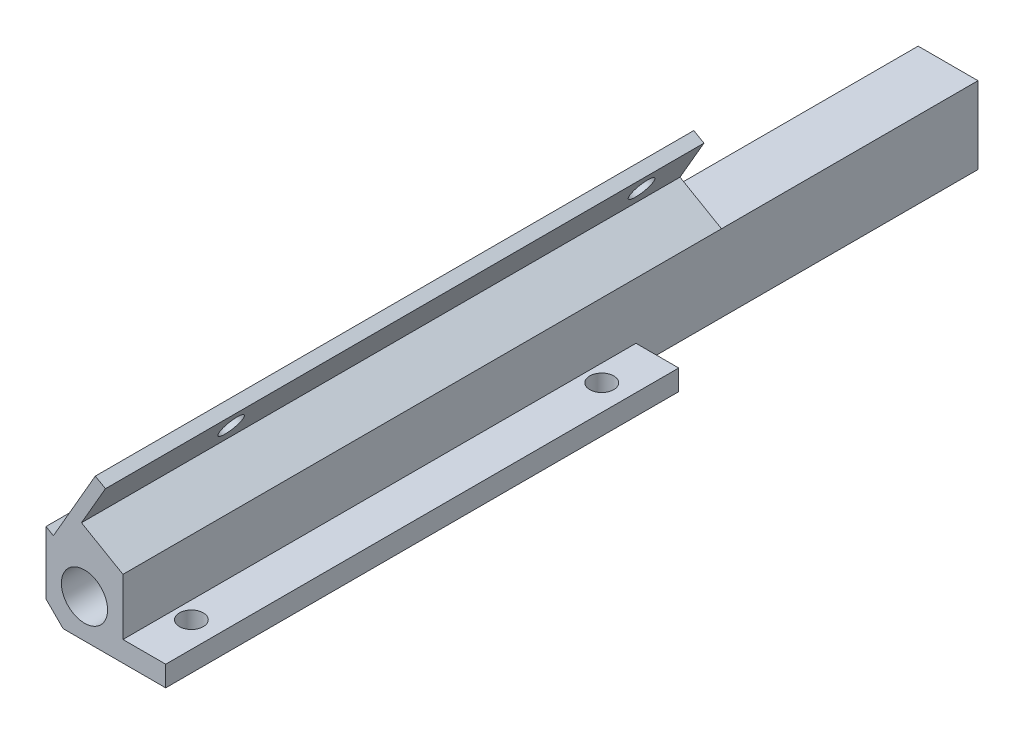
SolidWorks part; units mm, degrees
ref_plane "Front Plane" through (0, 0, 0) normal (0, 0, 1) x (1, 0, 0)
ref_plane "Top Plane" through (0, 0, 0) normal (0, 1, 0) x (1, 0, 0)
ref_plane "Right Plane" through (0, 0, 0) normal (1, 0, 0) x (0, 0, -1)
sketch "Sketch1" plane through (0, 0, 0) normal (0, 1, 0) x (1, 0, 0)
  line L1 (0, 0) -> (77.47, 0)
  line L2 (0, 0) -> (0, 127)
  line L3 (0, 127) -> (77.47, 127)
  line L4 (77.47, 0) -> (77.47, 127)
  dimension "D1" = 77.47
  dimension "D2" = 127
extrude "Boss-Extrude1" add sketch "Sketch1" along normal blind 11.43
sketch "Sketch2" plane through (0, 0, 0) normal (0, 0, 1) x (1, 0, 0)
  line L0 (5.715, 5.715) -> (71.755, 5.715) construction
  line L1 (38.735, 11.43) -> (38.735, 0) construction
  line L2 (0, 11.43) -> (77.47, 11.43) construction
  line L3 (0, 0) -> (77.47, 0) construction
  circle A0 centre (5.715, 5.715) radius 3.429
  circle A1 centre (71.755, 5.715) radius 3.429
  point P10 (38.735, 5.715)
  dimension "D1" = 6.858
  dimension "D2" = 66.04
extrude "Cut-Extrude1" cut sketch "Sketch2" against normal through all
sketch "Sketch3" plane through (0, 11.43, 0) normal (0, 1, 0) x (1, 0, 0)
  line L0 (11.43, 127) -> (11.43, 88.9)
  line L1 (77.47, 127) -> (0, 127) construction
  line L2 (11.43, 127) -> (66.04, 127)
  line L3 (66.04, 127) -> (66.04, 88.9)
  line L4 (53.34, 76.2) -> (24.13, 76.2)
  line L5 (0, 127) -> (0, 0) construction
  arc A0 (66.04, 88.9) -> (53.34, 76.2) centre (53.34, 88.9) cw
  arc A1 (24.13, 76.2) -> (11.43, 88.9) centre (24.13, 88.9) cw
  point P10 (38.735, 127)
  dimension "D1" = 12.7
  dimension "D2" = 11.43
  dimension "D3" = 50.8
extrude "Cut-Extrude2" cut sketch "Sketch3" against normal through all
sketch "Sketch4" plane through (0, 0, -127) normal (0, 0, -1) x (-1, 0, 0)
  line L0 (-11.43, 0) -> (-11.43, 11.43) construction
  line L1 (-66.04, 11.43) -> (-11.43, 11.43)
  line L2 (-66.04, 11.43) -> (-66.04, 5.08)
  line L3 (-66.04, 5.08) -> (-11.43, 5.08)
  line L4 (-11.43, 11.43) -> (-11.43, 5.08)
  line L5 (-11.43, 0) -> (0, 0) construction
  dimension "D1" = 5.08
extrude "Cut-Extrude3" cut sketch "Sketch4" against normal through all
chamfer "Chamfer1" distance 2.54 angle 45 4 edges at (0, 0, -63.5) (0, 11.43, -63.5) (77.47, 0, -63.5) (77.47, 11.43, -63.5)
sketch "Sketch5" plane through (0, 11.43, 0) normal (0, 1, 0) x (1, 0, 0)
  line L0 (11.43, 88.9) -> (11.43, 76.2)
  line L1 (11.43, 0) -> (11.43, 88.9) construction
  line L2 (11.43, 76.2) -> (77.47, 76.2)
  line L3 (77.47, 127) -> (77.47, 0) construction
  line L4 (77.47, 76.2) -> (77.47, 127)
  line L8 (24.13, 76.2) -> (53.34, 76.2) construction
  line L9 (77.47, 127) -> (11.43, 127)
  line L10 (11.43, 127) -> (11.43, 88.9)
extrude "Cut-Extrude4" cut sketch "Sketch5" against normal through all
sketch "Sketch6" plane through (0, 11.43, 0) normal (0, 1, 0) x (1, 0, 0)
  line L0 (24.13, 76.2) -> (24.13, 0)
  line L1 (11.43, 76.2) -> (66.04, 76.2) construction
  line L2 (66.04, 0) -> (11.43, 0) construction
  line L3 (24.13, 0) -> (77.47, 0)
  line L4 (77.47, 0) -> (77.47, 76.2)
  line L5 (77.47, 76.2) -> (24.13, 76.2)
  line L6 (11.43, 0) -> (11.43, 76.2) construction
  dimension "D1" = 12.7
extrude "Cut-Extrude5" cut sketch "Sketch6" against normal through all
sketch "Sketch7" plane through (0, 5.08, 0) normal (0, 1, 0) x (1, 0, 0)
  line L0 (11.43, 76.2) -> (24.13, 76.2) construction
  line L1 (11.43, 0) -> (11.43, 76.2) construction
  circle A0 centre (13.97, 68.58) radius 1.778
  circle A1 centre (13.97, 7.62) radius 1.778
  dimension "D1" = 3.556
  dimension "D2" = 7.62
  dimension "D3" = 68.58
  dimension "D4" = 2.54
extrude "Hole Cuts 1" cut sketch "Sketch7" against normal through all
sketch "Sketch17" plane through (0, 0, 0) normal (0, 0, 1) x (1, 0, 0)
  line L0 (0, 8.89) -> (0, 11.8699)
  line L1 (0, 11.8699) -> (5.588, 21.5486)
  line L2 (5.588, 21.5486) -> (8.8517, 19.6643)
  line L3 (8.8517, 19.6643) -> (5.9307, 14.605)
  line L4 (5.9307, 14.605) -> (11.43, 11.43)
  line L5 (0, 8.89) -> (0, 2.54) construction
  line L6 (11.43, 11.43) -> (2.54, 11.43)
  line L7 (2.54, 11.43) -> (0, 8.89)
  dimension "D1" = 11.176
  dimension "D2" = 5.842
  dimension "D3" = 6.35
  dimension "D4" = 60
extrude "Boss-Extrude5" add sketch "Sketch17" against normal blind 88.9
sketch "Sketch18" plane through (0, 0, 0) normal (0, 0, 1) x (1, 0, 0)
  line L0 (2.54, 0) -> (17.78, 0) construction
  line L1 (2.54, 0) -> (24.13, 0) construction
  line L2 (11.43, 5.08) -> (11.43, 11.43) construction
  line L3 (17.78, 0) -> (24.13, 0)
  line L4 (24.13, 0) -> (24.13, 5.08)
  line L5 (24.13, 5.08) -> (17.78, 5.08)
  line L6 (24.13, 5.08) -> (11.43, 5.08) construction
  line L7 (17.78, 5.08) -> (17.78, 0)
  dimension "D1" = 6.35
extrude "Cut-Extrude13" cut sketch "Sketch18" against normal blind 76.2
sketch "Sketch19" plane through (-1.8761, 1.0832, 0) normal (0.866, -0.5, 0) x (0, 0, -1)
  line L1 (88.9, 15.6137) -> (0, 15.6137) construction
  line L2 (88.9, 15.6137) -> (88.9, 21.4557) construction
  circle A0 centre (20.32, 19.4237) radius 1.778
  circle A1 centre (81.28, 19.4237) radius 1.778
  dimension "D1" = 3.556
  dimension "D2" = 7.62
  dimension "D3" = 68.58
  dimension "D4" = 3.81
extrude "Hole Cuts 2" cut sketch "Sketch19" against normal up to next
sketch "Sketch20" plane through (-5.1398, 2.9675, 0) normal (-0.866, 0.5, 0) x (0, 0, 1)
  line L1 (-88.9, 21.4557) -> (0, 21.4557)
  line L2 (-88.9, 21.4557) -> (-88.9, 10.2797)
  line L3 (-88.9, 10.2797) -> (0, 10.2797)
  line L4 (0, 21.4557) -> (0, 10.2797)
extrude "Cut-Extrude16" cut sketch "Sketch20" against normal blind 1.27
sketch "Sketch21" plane through (-1.8761, 1.0832, 0) normal (0.866, -0.5, 0) x (0, 0, -1)
  line L1 (88.9, 21.4557) -> (0, 21.4557)
  line L2 (88.9, 21.4557) -> (88.9, 15.6137)
  line L3 (88.9, 15.6137) -> (0, 15.6137)
  line L4 (0, 21.4557) -> (0, 15.6137)
extrude "Cut-Extrude17" cut sketch "Sketch21" against normal blind 0.762
sketch "Sketch22" plane through (0, 5.08, 0) normal (0, 1, 0) x (1, 0, 0)
  line L1 (17.78, 0) -> (11.43, 0)
  line L2 (17.78, 0) -> (17.78, 76.2)
  line L3 (17.78, 76.2) -> (11.43, 76.2)
  line L4 (11.43, 0) -> (11.43, 76.2)
extrude "Cut-Extrude18" cut sketch "Sketch22" against normal blind 2.032
sketch "Sketch23" plane through (10.7278, 18.5812, 0) normal (0.5, 0.866, 0) x (0.866, -0.5, 0)
  line L1 (-4.665, 88.9) -> (-2.9283, 88.9)
  line L2 (-4.665, 88.9) -> (-4.665, 0)
  line L3 (-4.665, 0) -> (-2.9283, 0)
  line L4 (-2.9283, 88.9) -> (-2.9283, 0)
extrude "Boss-Extrude6" add sketch "Sketch23" along normal blind 1.27
